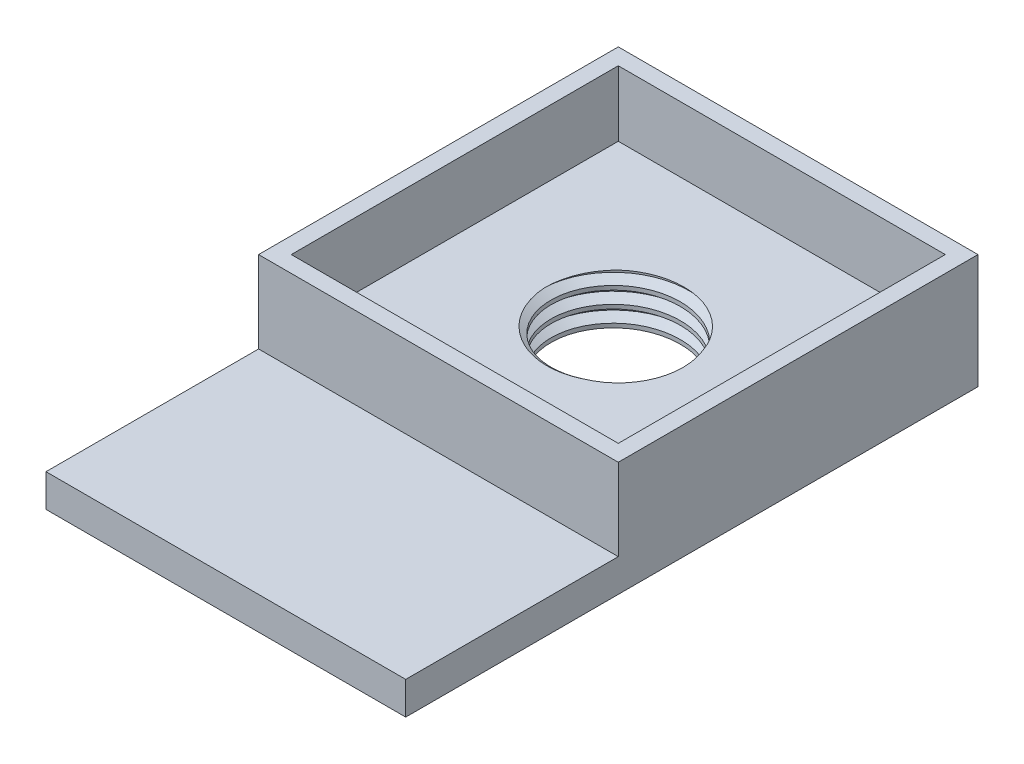
SolidWorks part; units mm, degrees
note: The reader was unsure of these and kept them because the rebuilt part matched: shared geometry of "Sketch1<2>", "Sketch2<3>".
ref_plane "Front Plane" through (0, 0, 0) normal (0, 0, 1) x (1, 0, 0)
ref_plane "Top Plane" through (0, 0, 0) normal (0, 1, 0) x (1, 0, 0)
ref_plane "Right Plane" through (0, 0, 0) normal (1, 0, 0) x (0, 0, -1)
sketch "Sketch1" plane through (0, 0, 0) normal (0, 1, 0) x (1, 0, 0)
  line L1 (-10, -10) -> (10, -10)
  line L2 (-10, -10) -> (-10, 10)
  line L3 (-10, 10) -> (10, 10)
  line L4 (10, -10) -> (10, 10)
  line L5 (-10, -10) -> (10, 10) construction
  line L6 (-10, 10) -> (10, -10) construction
  line L7 (-11, -11) -> (11, -11)
  line L8 (-11, -11) -> (-11, 11)
  line L9 (-11, 11) -> (11, 11)
  line L10 (11, -11) -> (11, 11)
  line L11 (-11, -11) -> (11, 11) construction
  line L12 (-11, 11) -> (11, -11) construction
  point P0 (0, 0)
  point P6 (0, 0)
  dimension "D1" = 20
  dimension "D2" = 20
  dimension "D3" = 22
  dimension "D4" = 22
extrude "Boss-Extrude1" add sketch "Sketch1" along normal blind 5 and the other way blind 2
extrude "Boss-Extrude2" add sketch "Sketch1<2>" along normal blind 1 and the other way blind 2 contours L1 L4 L3 L2
sketch "Sketch1<2>" plane through (0, 0, 0) normal (0, 1, 0) x (1, 0, 0) same geometry as "Sketch1"
sketch "Sketch2" plane through (0, -2, 0) normal (0, -1, 0) x (1, 0, 0)
  circle A0 centre (0, 0) radius 4.5
  circle A1 centre (0, 0) radius 7
  dimension "D1" = 9
extrude "Cut-Extrude1" cut sketch "Sketch2<3>" against normal blind 7 contours A0
sketch "Sketch2<3>" plane through (0, -2, 0) normal (0, -1, 0) x (1, 0, 0) same geometry as "Sketch2"
sketch "Sketch3" plane through (0, 0, 0) normal (0, 1, 0) x (1, 0, 0)
  line L0 (0, -11) -> (0, -24)
  line L1 (-11, -11) -> (11, -11)
  line L2 (-11, -11) -> (-11, -24)
  line L3 (-11, -24) -> (11, -24)
  line L4 (11, -11) -> (11, -24)
  line L5 (-10.75, -24) -> (0, -24)
  line L6 (-8, -20) -> (-8, -24)
  line L7 (-10.75, -24) -> (-9.9027, -24)
  line L8 (-8, -20) -> (8, -20)
  line L9 (-8, -24) -> (8, -24)
  line L10 (-10.75, -24) -> (-13.75, -24)
  line L11 (0, -24) -> (-2.0006, -24)
  line L12 (0, -24) -> (-1, -24)
  line L13 (-11, 11) -> (-11, -11) construction
  line L14 (-1, -24) -> (-1, -21.75)
  line L15 (0, -24) -> (-3, -24)
  line L16 (10.75, -24) -> (13.75, -24)
  line L17 (8, -20) -> (8, -24)
  line L18 (-8, -20) -> (8, -24) construction
  line L19 (-8, -24) -> (8, -20) construction
  line L20 (-11, -9) -> (-11, -11)
  line L21 (11, -9) -> (11, -11)
  line L22 (10.75, -24) -> (0, -24)
  line L23 (-8, -20) -> (-3, -24)
  line L24 (1, -24) -> (1, -21.75)
  line L25 (8, -20) -> (3, -24)
  spline S0 degree 1 poles (-8, -20) (-1, -21.75) knots 0 0 1 1
  spline S1 degree 1 poles (8, -20) (1, -21.75) knots 0 0 1 1
  point P9 (0, -22)
  dimension "D1" = 10.75
  dimension "D3" = 13
  dimension "D4" = 3
  dimension "D5" = 4
  dimension "D9" = 0
extrude "Boss-Extrude3" add sketch "Sketch3" against normal blind 2 contours L8 L17 L3 L4 L1 L0 | L6 L8 L0 L1 L2 L3 L5 | L8 S0 L14 L11 L0 | S0 L23 L9 L14 | L23 L6 L5 | S1 L8 L0 L3 L24 | L25 S1 L24 L22 | L17 L25 L3
thread "Thread2" pitch 1 start angle 0, offset 1, length 10, pitch 1, diameter 9
ref_plane "Plane3" through (-4.5, 2, 0) normal (0, 0, 1) x (-1, 0, 0)
sketch "Thread Profile3" plane through (-4.5, 2, 0) normal (0, 0, 1) x (-1, 0, 0)
  line L0 (0, 0) -> (0, 1) construction
  line L11 (0, 0) -> (0, 0.875)
  line L12 (0, 0.875) -> (-0.5413, 0.5625)
  line L13 (-0.5413, 0.5625) -> (-0.5413, 0.3125)
  line L15 (-0.5413, 0.3125) -> (0, 0)
  line L17 (-0.5413, 0.4375) -> (0, 0.4375) construction
  point P2 (0, 0)
  dimension "Pitch" = 1
  dimension "Profile_Angle" = 60
  dimension "Profile_Land" = 0.25
  dimension "Profile_Height" = 0.5413
